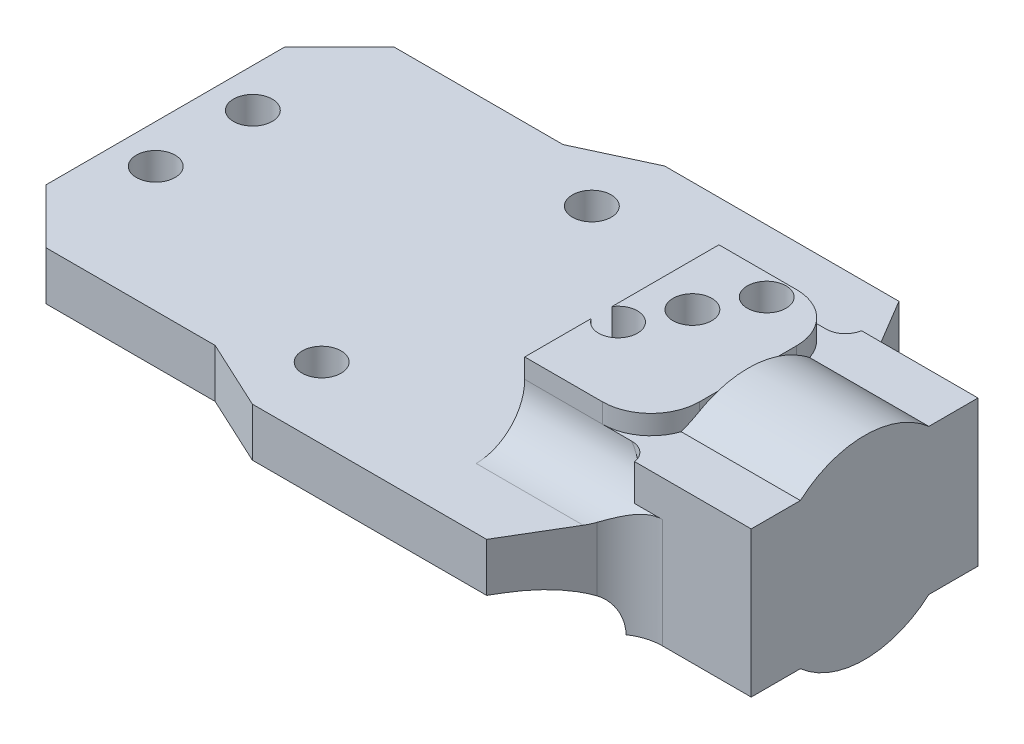
SolidWorks part; units mm, degrees
material "ABS PC"
ref_plane "Plan de face" through (0, 0, 0) normal (0, 0, 1) x (1, 0, 0)
ref_plane "Plan de dessus" through (0, 0, 0) normal (0, 1, 0) x (1, 0, 0)
ref_plane "Plan de droite" through (0, 0, 0) normal (1, 0, 0) x (0, 0, -1)
sketch "Esquisse1" plane through (0, 0, 0) normal (0, 1, 0) x (1, 0, 0)
  line L0 (0, -17.2592) -> (0, 7.3408)
  line L1 (0, 7.3408) -> (5.6122, 12.9531)
  line L2 (5.6122, 12.9531) -> (23.0322, 12.9531)
  line L4 (-4.0801, -4.9592) -> (35.6864, -4.9592) construction
  line L5 (5.6122, -22.8714) -> (23.0322, -22.8714)
  line L6 (0, -17.2592) -> (5.6122, -22.8714)
  line L7 (23.0322, 12.9531) -> (30.1774, 16.2726)
  line L8 (30.1774, 16.2726) -> (54.3076, 16.2726)
  line L9 (54.3076, 16.2726) -> (60, 6.7185)
  line L10 (60, 6.7185) -> (60, -16.6369)
  line L11 (23.0322, -22.8714) -> (30.1774, -26.191)
  line L12 (30.1774, -26.191) -> (54.3076, -26.191)
  line L13 (54.3076, -26.191) -> (60, -16.6369)
  circle A0 centre (4, 0.0408) radius 2
  circle A1 centre (30, 8.9531) radius 2
  circle A2 centre (30, -18.8714) radius 2
  circle A3 centre (4, -9.9592) radius 2
  point P17 (35.6122, -4.9592)
  point P19 (0, -4.9592)
  point P29 (60, -4.9592)
  dimension "D3" = 5
  dimension "D7" = 4
  dimension "D8" = 4
  dimension "D1" = 12.3
  dimension "D4" = 4
  dimension "D5" = 4
  dimension "D6" = 30
  dimension "D9" = 60
extrude "Boss.-Extru.1" add sketch "Esquisse1" along normal blind 5
sketch "Esquisse2" plane through (0, 5, 0) normal (0, 1, 0) x (1, 0, 0)
  line L0 (60, -16.6369) -> (60, 6.7185) construction
  line L1 (60, -14.9592) -> (47, -14.9592)
  line L2 (60, -14.9592) -> (60, 5.0408)
  line L3 (60, 5.0408) -> (47, 5.0408)
  line L4 (47, -14.9592) -> (47, 5.0408)
  point P4 (60, -4.9592)
  point P7 (60, -4.9592)
  dimension "D1" = 13
  dimension "D2" = 20
  dimension "D3" = 0
extrude "Boss.-Extru.2" add sketch "Esquisse2" along normal blind 7
sketch "Esquisse3" plane through (60, 0, 0) normal (1, 0, 0) x (0, 0, -1)
  line L0 (-16.6369, 2.5) -> (-16.6369, 10)
  line L1 (-16.6369, 5) -> (-16.6369, 0) construction
  line L3 (-16.6369, 2.5) -> (-16.6369, -5)
  line L4 (6.7185, 2.5) -> (6.7185, -5)
  line L5 (6.7185, 5) -> (6.7185, 0) construction
  line L7 (6.7185, 10) -> (6.7185, 2.5)
  line L8 (-16.6369, -5) -> (-11.5736, -5)
  line L9 (1.6552, -5) -> (6.7185, -5)
  line L10 (-16.6369, 10) -> (-11.5736, 10)
  line L11 (6.7185, 10) -> (1.6552, 10)
  circle A0 centre (-4.9592, 2.5) radius 10 construction
  arc A1 (-11.5736, -5) -> (1.6552, -5) centre (-4.9592, 2.5) ccw
  arc A2 (1.6552, 10) -> (-11.5736, 10) centre (-4.9592, 2.5) ccw
  dimension "D3" = 20
  dimension "D1" = 23.3554
extrude "Boss.-Extru.3" add sketch "Esquisse3" along normal blind 12
fillet "Congé5" radius 2 2 edges at (60, 7.5, -5.0408) (60, 7.5, 14.9592)
fillet "Congé6" radius 5 1 edges at (60, 0, 4.9592)
fillet "Congé7" radius 5 2 edges at (60, 0, 16.6369) (60, 0, -6.7185)
fillet "Congé8" radius 5 2 edges at (52.5131, 5, -5.0408) (52.5131, 5, 14.9592)
fillet "Congé9" radius 5 2 edges at (60, 11, 14.9592) (60, 11, -5.0408)
sketch "Esquisse4" plane through (0, 12, 0) normal (0, 1, 0) x (1, 0, 0)
  line L0 (47, 5.0408) -> (54.1178, 2.8408) construction
  line L1 (54.1178, 2.8408) -> (54.1178, 5.0408) construction
  line L2 (55, 5.0408) -> (47, 5.0408) construction
  line L3 (47, 5.0408) -> (51.406, -2.0992) construction
  line L4 (51.406, -2.0992) -> (51.406, 5.0408) construction
  line L5 (55, 5.0408) -> (47, 5.0408) construction
  line L6 (54.1178, 2.8408) -> (47.6758, -8.8942) construction
  circle A0 centre (54.1178, 2.8408) radius 2
  circle A1 centre (51.406, -2.0992) radius 2
  circle A2 centre (48.6919, -7.0432) radius 2
  dimension "D3" = 4
  dimension "D6" = 4
  dimension "D7" = 4
  dimension "D1" = 2.2
  dimension "D2" = 7.45
  dimension "D4" = 8.39
  dimension "D5" = 7.14
  dimension "D8" = 5.64
extrude "Enlèv. mat.-Extru.1" cut sketch "Esquisse4" against normal through all
